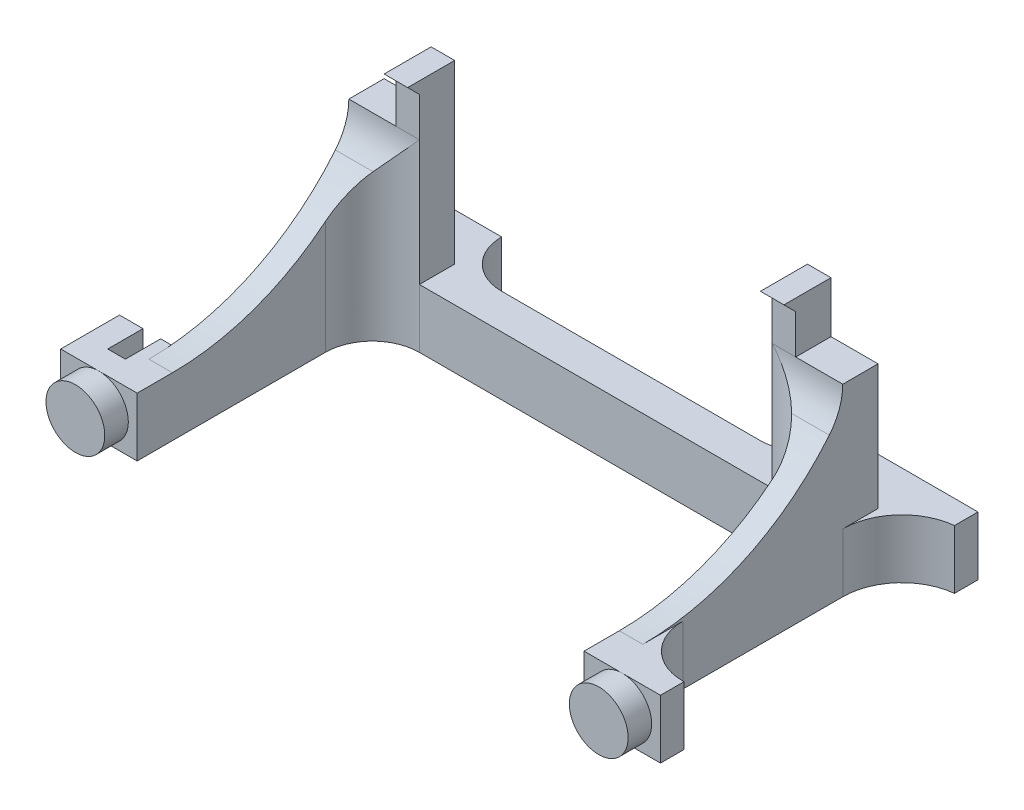
SolidWorks part; units mm, degrees
material "PLA"
ref_plane "Front Plane" through (0, 0, 0) normal (0, 0, 1) x (1, 0, 0)
ref_plane "Top Plane" through (0, 0, 0) normal (0, 1, 0) x (1, 0, 0)
ref_plane "Right Plane" through (0, 0, 0) normal (1, 0, 0) x (0, 0, -1)
sketch "Sketch1" plane through (0, 0, 0) normal (0, 1, 0) x (1, 0, 0)
  line L0 (-19, -10) -> (19, -10) construction
  line L1 (-19, -10) -> (-19, 10)
  line L2 (-19, 10) -> (19, 10)
  line L3 (19, -10) -> (19, 10)
  line L4 (-19, -10) -> (19, 10) construction
  line L5 (-19, 10) -> (19, -10) construction
  line L6 (-19, -10) -> (-25.5, -10)
  line L7 (-25.5, -10) -> (-25.5, -5)
  line L8 (-25.5, -5) -> (-23.5, -5)
  line L9 (-23.5, -5) -> (-23.5, -8)
  line L10 (-23.5, -8) -> (-22, -8)
  line L11 (-22, -8) -> (-22, -5)
  line L12 (-22, -5) -> (-21, -5)
  line L13 (-21, -5) -> (-21, 12)
  line L14 (-21, 3.5) -> (-25.5, 3.5) construction
  line L15 (-22, 12) -> (-21, 12)
  line L16 (-22, 15) -> (-22, 12)
  line L17 (-23.5, 15) -> (-22, 15)
  line L18 (-23.5, 12) -> (-23.5, 15)
  line L19 (-25.5, 12) -> (-23.5, 12)
  line L20 (-25.5, 17) -> (-25.5, 12)
  line L21 (-25.5, 17) -> (-19, 17)
  line L22 (-19, 17) -> (-19, 13) construction
  line L23 (-11, 13) -> (11, 13)
  line L24 (0, -996.1823) -> (0, 49003.8177) construction
  line L25 (19, -10) -> (25.5, -10)
  line L33 (22, 12) -> (21, 12) construction
  line L34 (25.5, 12) -> (23.5, 12) construction
  line L35 (23.5, 15) -> (22, 15) construction
  line L36 (22, 15) -> (22, 12) construction
  line L37 (23.5, 12) -> (23.5, 15) construction
  line L38 (25.5, 17) -> (25.5, 12) construction
  line L39 (25.5, 17) -> (19, 17)
  line L40 (19, 17) -> (19, 13) construction
  line L45 (25.5, -8) -> (25.5, -10)
  line L47 (25.5, 17) -> (25.5, 15)
  line L48 (-19, 13) -> (-15, 13) construction
  line L49 (15, 13) -> (19, 13) construction
  line L50 (25.4, -8) -> (25.5, -8)
  line L51 (21, 10) -> (21, -3.6)
  line L53 (11, 13) -> (15, 13) construction
  line L54 (19, 17) -> (15, 17)
  line L55 (-19, 17) -> (-15, 17)
  line L56 (-15, 13) -> (-11, 13) construction
  arc A0 (21, 10) -> (25.5, 15) centre (26.0278, 10) cw
  arc A1 (19, 17) -> (15, 13) centre (15, 17) cw construction
  arc A2 (-19, 17) -> (-15, 13) centre (-15, 17) ccw construction
  arc A3 (21, -3.6) -> (25.4, -8) centre (25.4, -3.6) ccw
  arc A4 (11, 13) -> (15, 17) centre (11, 17) ccw
  arc A5 (-15, 17) -> (-11, 13) centre (-11, 17) ccw
  point P0 (0, 0)
  point P42 (0, 10)
  dimension "D11" = 2
  dimension "D12" = 2
  dimension "D13" = 4.4
  dimension "D1" = 38
  dimension "D2" = 20
  dimension "D3" = 23
  dimension "D4" = 3
  dimension "D5" = 2
  dimension "D6" = 1
  dimension "D7" = 1.5
  dimension "D8" = 2
  dimension "D9" = 2
  dimension "D10" = 3
  dimension "D14" = 4
  dimension "D15" = 4
extrude "Boss-Extrude1" add sketch "Sketch1" along normal mid plane 5 contours L23 L22 L21 L20 L19 L18 L17 L16 L15 L13 L12 L11 L10 L9 L8 L7 L6 L1 L2 L3 L25 L45 region at (-22.25, 0, 9.4229)
sketch "Sketch2" plane through (0, 0, 10) normal (0, 0, 1) x (1, 0, 0)
  line L4 (22.25, 2.5) -> (22.25, -2.5) construction
  line L5 (0, -11) -> (0, 11) construction
  line L6 (19, 2.5) -> (25.5, 2.5) construction
  line L7 (19, -2.5) -> (25.5, -2.5) construction
  line L8 (-22.25, 2.5) -> (-22.25, -2.5) construction
  circle A1 centre (22.25, 0) radius 2.5
  circle A2 centre (-22.25, 0) radius 2.5
  point P6 (22.25, 2.5)
  point P19 (22.25, -2.5)
extrude "Boss-Extrude2" add sketch "Sketch2" along normal blind 2
sketch "Sketch4" plane through (0, 0, 0) normal (1, 0, 0) x (0, 0, -1)
  line L0 (13, 2.5) -> (-7, 2.5)
  line L1 (13, 2.5) -> (13, 13.1573)
  line L2 (13, 17.5) -> (9, 17.5) construction
  line L3 (9, 17.5) -> (10, 16.5) construction
  line L4 (10, 16.5) -> (10, 13.1573) construction
  line L5 (10, 13.1573) -> (13, 13.1573)
  line L6 (13, 13.1573) -> (13, 17.5) construction
  arc A0 (-7, 2.5) -> (8.8571, 9.9757) centre (-7, 23.0556) ccw
  arc A1 (10, 13.1573) -> (8.8571, 9.9757) centre (5, 13.1573) cw
  point P1 (-7, 2.5)
  point P9 (10, 11.5)
  dimension "D1" = 5
  dimension "D7" = 20
  dimension "D2" = 4
  dimension "D3" = 1
  dimension "D4" = 45
  dimension "D5" = 5
  dimension "D6" = 15
extrude "Boss-Extrude3" add sketch "Sketch4" along direction (1, 0, 0) on the side of the normal up to surface (21 mm away) from surface up to face at (21, 0, -3.2) starting at face at (19, 0, 0)
extrude "Boss-Extrude4" add sketch "Sketch4<2>" against normal up to surface (21 mm away) from surface up to face at (-21, 0, -3.5) starting at face at (-19, 0, 0)
sketch "Sketch4<2>" plane through (0, 0, 0) normal (1, 0, 0) x (0, 0, -1) same geometry as "Sketch4"
sketch "Sketch5" plane through (0, 0, 0) normal (1, 0, 0) x (0, 0, -1)
  line L0 (13, 13.1573) -> (13, 17.5) construction
  line L1 (13, 17.5) -> (9, 17.5) construction
  line L2 (9, 17.5) -> (10, 16.5) construction
  line L3 (10, 16.5) -> (10, 13.1573) construction
  line L4 (13, 13.1573) -> (13, 17.5)
  line L5 (13, 17.5) -> (9, 17.5)
  line L6 (9, 17.5) -> (10, 16.5)
  line L7 (10, 16.5) -> (10, 13.1573)
  line L8 (10, 13.1573) -> (10, 2.5)
  line L9 (10, 2.5) -> (13, 2.5)
  line L10 (13, 2.5) -> (13, 13.1573)
extrude "Boss-Extrude5" add sketch "Sketch5" along normal blind 2 from offset 15
sketch "Sketch6" plane through (0, 0, -10) normal (0, 0, 1) x (1, 0, 0)
  line L0 (19, 13.1573) -> (17, 13.1573)
  line L1 (17, 16.5) -> (17, 2.5) construction
  line L2 (19, 13.1573) -> (19, 9.9757) construction
  line L3 (19, 9.9757) -> (19, 2.5) construction
  line L4 (17, 2.5) -> (19, 2.5) construction
  line L5 (19, 13.1573) -> (19, 9.9757)
  line L6 (19, 9.9757) -> (19, 2.5)
  line L7 (17, 2.5) -> (19, 2.5)
  line L8 (17, 13.1573) -> (17, 2.5)
extrude "Boss-Extrude6" add sketch "Sketch6" against normal up to surface (3 mm away) up to face at (16, 10, -13)
mirror "Mirror1" about plane through (0, 0, 0) normal (1, 0, 0) of "Boss-Extrude5", "Boss-Extrude6"
fillet "Fillet1" radius 4 2 edges at (19, 5.3287, -10) (-19, 5.3287, -10)
